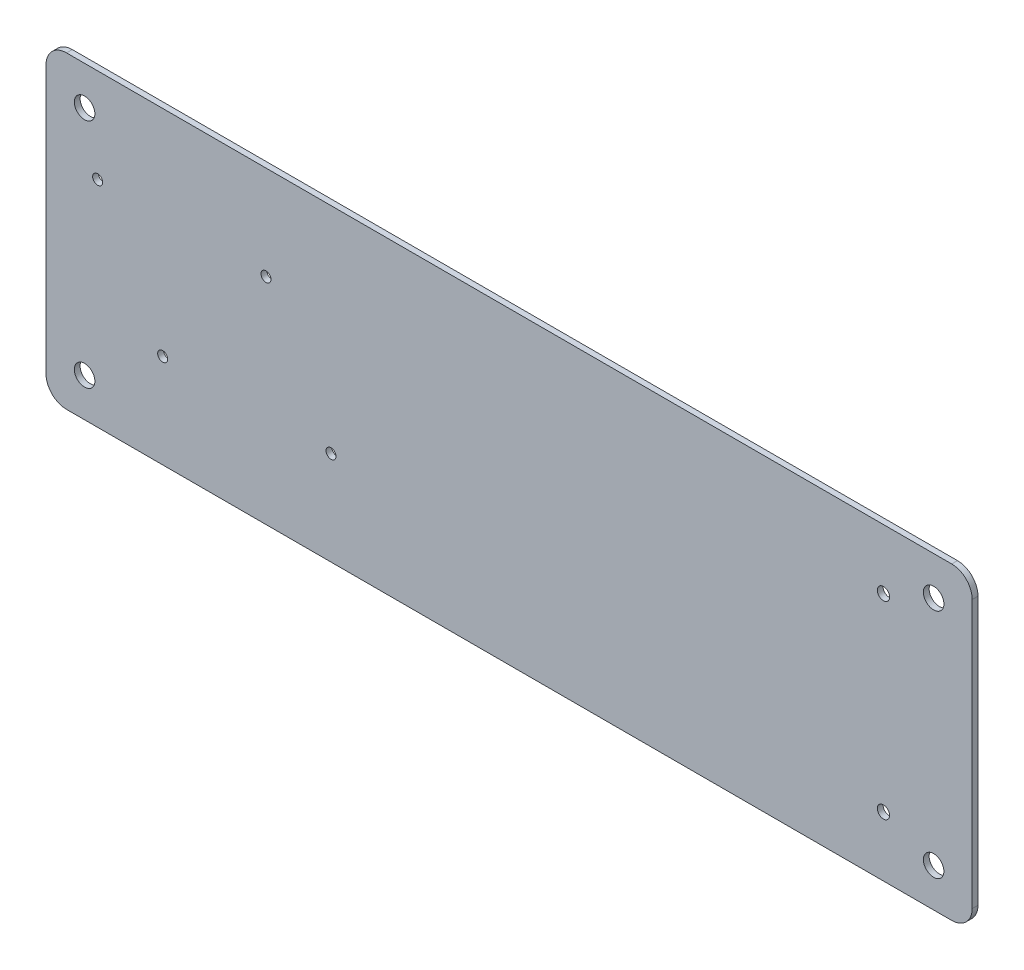
SolidWorks part; units mm, degrees
ref_plane "Front Plane" through (0, 0, 0) normal (0, 0, 1) x (1, 0, 0)
ref_plane "Top Plane" through (0, 0, 0) normal (0, 1, 0) x (1, 0, 0)
ref_plane "Right Plane" through (0, 0, 0) normal (1, 0, 0) x (0, 0, -1)
sketch "Sketch1" plane through (0, 0, 0) normal (0, 0, 1) x (1, 0, 0)
  line L1 (-145.6436, -50.8) -> (145.6436, -50.8)
  line L2 (-152.4, -44.0436) -> (-152.4, 44.0436)
  line L3 (-145.6436, 50.8) -> (145.6436, 50.8)
  line L4 (152.4, -44.0436) -> (152.4, 44.0436)
  line L5 (-152.4, -50.8) -> (152.4, 50.8) construction
  line L6 (-152.4, 50.8) -> (152.4, -50.8) construction
  arc A0 (145.6436, -50.8) -> (152.4, -44.0436) centre (145.6436, -44.0436) ccw
  arc A1 (-152.4, 44.0436) -> (-145.6436, 50.8) centre (-145.6436, 44.0436) cw
  arc A2 (-145.6436, -50.8) -> (-152.4, -44.0436) centre (-145.6436, -44.0436) cw
  arc A3 (145.6436, 50.8) -> (152.4, 44.0436) centre (145.6436, 44.0436) cw
  point P0 (0, 0)
  dimension "D3" = 6.7564
  dimension "D1" = 101.6
  dimension "D2" = 304.8
extrude "Boss-Extrude1" add sketch "Sketch1" along normal blind 1.9
sketch "Sketch2" plane through (0, 0, 0) normal (0, 0, -1) x (-1, 0, 0)
  line L0 (-139.7, 38.1) -> (-139.7, -38.1) construction
  line L1 (-139.7, 38.1) -> (139.7, 38.1) construction
  line L5 (55, 0) -> (-55, 0) construction
  line L6 (0, 55) -> (0, -55) construction
  circle A0 centre (-139.7, 38.1) radius 3.3782
  circle A1 centre (-139.7, -38.1) radius 3.3782
  circle A2 centre (139.7, 38.1) radius 3.3782
  circle A3 centre (139.7, -38.1) radius 3.3782
  point P4 (0, 0)
  dimension "D1" = 6.7564
  dimension "D2" = 76.2
  dimension "D3" = 279.4
extrude "Cut-Extrude1" cut sketch "Sketch2" against normal up to next and the other way through all
sketch "Sketch3" plane through (0, 0, 1.9) normal (0, 0, 1) x (1, 0, 0)
  circle A0 centre (-114, -19.85) radius 1.65
  arc A1 (-114, -21.5) -> (-114, -18.2) centre (-114, -19.85) ccw construction
  circle A2 centre (-135.4, 19.85) radius 1.65
  arc A3 (-135.4, 21.5) -> (-135.4, 18.2) centre (-135.4, 19.85) ccw construction
  circle A4 centre (-58.6, -19.85) radius 1.65
  arc A5 (-58.6, -18.2) -> (-58.6, -21.5) centre (-58.6, -19.85) ccw construction
  circle A6 centre (-80, 19.85) radius 1.65
  arc A7 (-80, 21.5) -> (-80, 18.2) centre (-80, 19.85) ccw construction
  circle A8 centre (123.19, -31.115) radius 2.0193
  circle A9 centre (123.19, 31.115) radius 2.0193
  ellipse E0 centre (123.19, 31.115) end of major axis (123.19, 33.1343) minor radius 2.0193 construction
  ellipse E1 centre (123.19, -31.115) end of major axis (121.1707, -31.115) minor radius 2.0193 construction
extrude "Cut-Extrude2" cut sketch "Sketch3" against normal up to next
